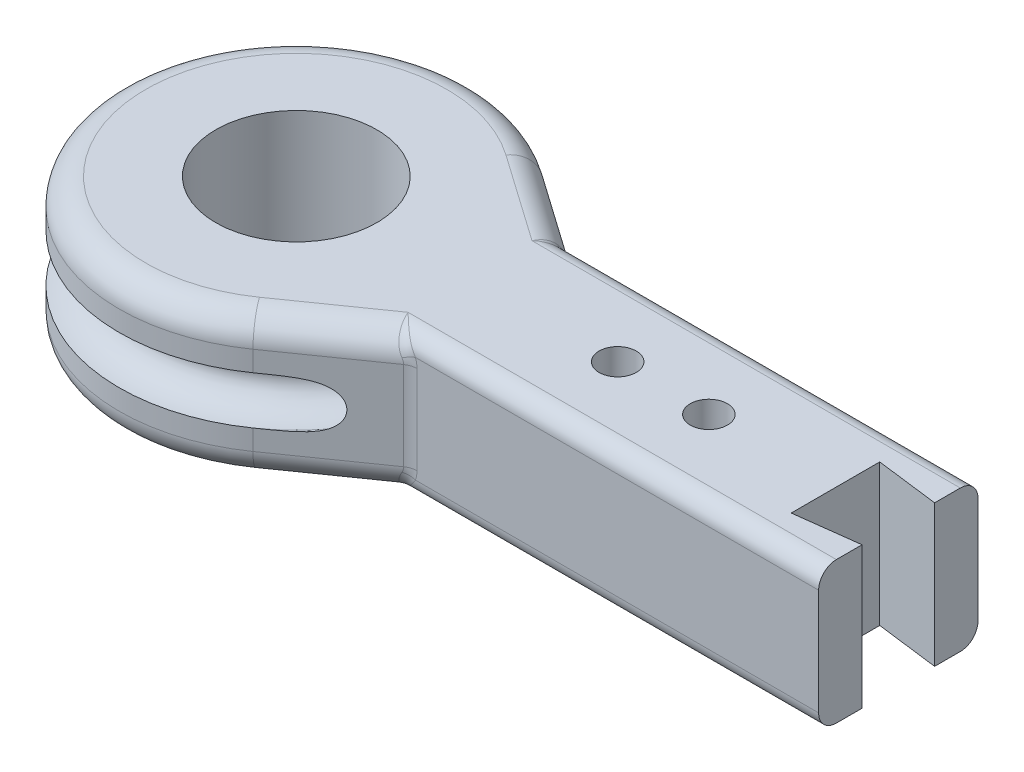
SolidWorks part; units mm, degrees
ref_plane "Front Plane" through (0, 0, 0) normal (0, 0, 1) x (1, 0, 0)
ref_plane "Top Plane" through (0, 0, 0) normal (0, 1, 0) x (1, 0, 0)
ref_plane "Right Plane" through (0, 0, 0) normal (1, 0, 0) x (0, 0, -1)
sketch "Sketch1" plane through (0, 0, 0) normal (0, 1, 0) x (1, 0, 0)
  line L0 (-12.4221, 0) -> (30.45, 0) construction
  line L1 (0, 8.1775) -> (0, -7.8417) construction
  line L2 (11, 4.5) -> (5.7415, 8.1875)
  line L3 (11, -4.5) -> (34, -4.5)
  line L5 (11, 4.5) -> (34, 4.5)
  line L6 (34, -4.5) -> (34, -2.05)
  line L7 (11, -4.5) -> (34, 4.5) construction
  line L8 (11, 4.5) -> (34, -4.5) construction
  line L9 (11, -4.5) -> (5.7415, -8.1875)
  line L10 (11, 4.5) -> (11, -4.5) construction
  line L21 (34, 2.05) -> (30.45, 2.5)
  line L23 (30.45, -2.5) -> (30.45, 2.5)
  line L26 (30.45, -2.5) -> (32.0606, -3.7411) construction
  line L27 (30.45, 2.5) -> (32.8953, 4.0677) construction
  line L28 (34, -2.05) -> (30.45, -2.5)
  line L30 (34, 2.05) -> (34, 4.5)
  arc A0 (5.7415, 8.1875) -> (5.7415, -8.1875) centre (0, 0) ccw
  circle A1 centre (0, 0) radius 4.55
  point P7 (22.5, 0)
  point P20 (-4.55, 0)
  point P44 (34, 2.05)
  point P48 (34, -2.05)
  dimension "D1" = 20
  dimension "D4" = 9.1
  dimension "D9" = 3.55
  dimension "D2" = 23
  dimension "D3" = 9
  dimension "D6" = 2
  dimension "D10" = 2
  dimension "D14" = 2.45
extrude "Boss-Extrude2" add sketch "Sketch1" along normal blind 8 contours A1 | L3 L6 L28 L23 L21 L30 L5 L2 A0 L9 region at (0, 0, 0)
sketch "Sketch4" plane through (-6.6668, 16.5353, 0) normal (0, 0, 1) x (0, 1, 0)
  line L2 (-8.5353, -12.4083) -> (-8.5353, 3.3332) construction
  line L3 (-8.5353, 3.3332) -> (-16.5353, 3.3332) construction
  line L8 (-16.5353, -6.6668) -> (-4.9826, -6.6668) construction
  ellipse E0 centre (-12.5353, 3.3332) end of major axis (-11.1853, 3.3332) minor radius 0.7 (-11.1853, 3.3332) -> (-13.8853, 3.3332) ccw
  ellipse E1 centre (-12.5353, 3.3332) end of major axis (-12.5353, 5.1332) minor radius 1.35 (-13.8853, 3.3332) -> (-11.1853, 3.3332) ccw
  point P0 (-12.5353, 3.3332)
  point P1 (-12.5353, 3.3332)
  point P13 (-8.5353, 3.3019)
  point P22 (-12.5353, 3.3332)
  dimension "D1" = 0.7
  dimension "D2" = 1.8
fillet "Fillet2" radius 1.5 6 edges at (8.3707, 0, -6.3438) (8.3707, 0, 6.3438) (8.3707, 8, -6.3438) (8.3707, 8, 6.3438) (-10, 0, 0) (-10, 8, 0)
sketch "Sketch5" plane through (0, 8, 0) normal (0, 1, 0) x (1, 0, 0)
  line L0 (11, 6.5426) -> (11, -6.3371) construction
  line L1 (30.45, 7.6045) -> (30.45, -7.4675) construction
  line L2 (0, 0) -> (39.1502, 0) construction
  circle A0 centre (18.15, 0) radius 1.05
  circle A1 centre (23.3, 0) radius 1.05
  point P0 (11, -4.5)
  point P1 (11, 4.5)
  point P16 (30.45, 0.0685)
  dimension "D2" = 2.1
  dimension "D1" = 7.15
  dimension "D3" = 7.15
extrude "Cut-Extrude1" cut sketch "Sketch5" against normal blind 10 contours A1 | A0
revolve "Cut-Revolve1" cut sketch "Sketch4" angle 360 about L8
fillet "Fillet3" radius 1 4 edges at (21.1937, 0, -4.5) (21.1937, 0, 4.5) (21.1937, 8, -4.5) (21.1937, 8, 4.5)
fillet "Fillet4" radius 1 5 edges at (10.3282, 7.7361, 4.1769) (10.9624, 6.7537, 4.5) (10.3282, 0.2639, 4.1769) (10.9624, 1.2463, 4.5) (11, 4, 4.5)
fillet "Fillet5" radius 1 5 edges at (10.3282, 0.2639, -4.1769) (10.3282, 7.7361, -4.1769) (10.9624, 1.2463, -4.5) (11, 4, -4.5) (10.9624, 6.7537, -4.5)
